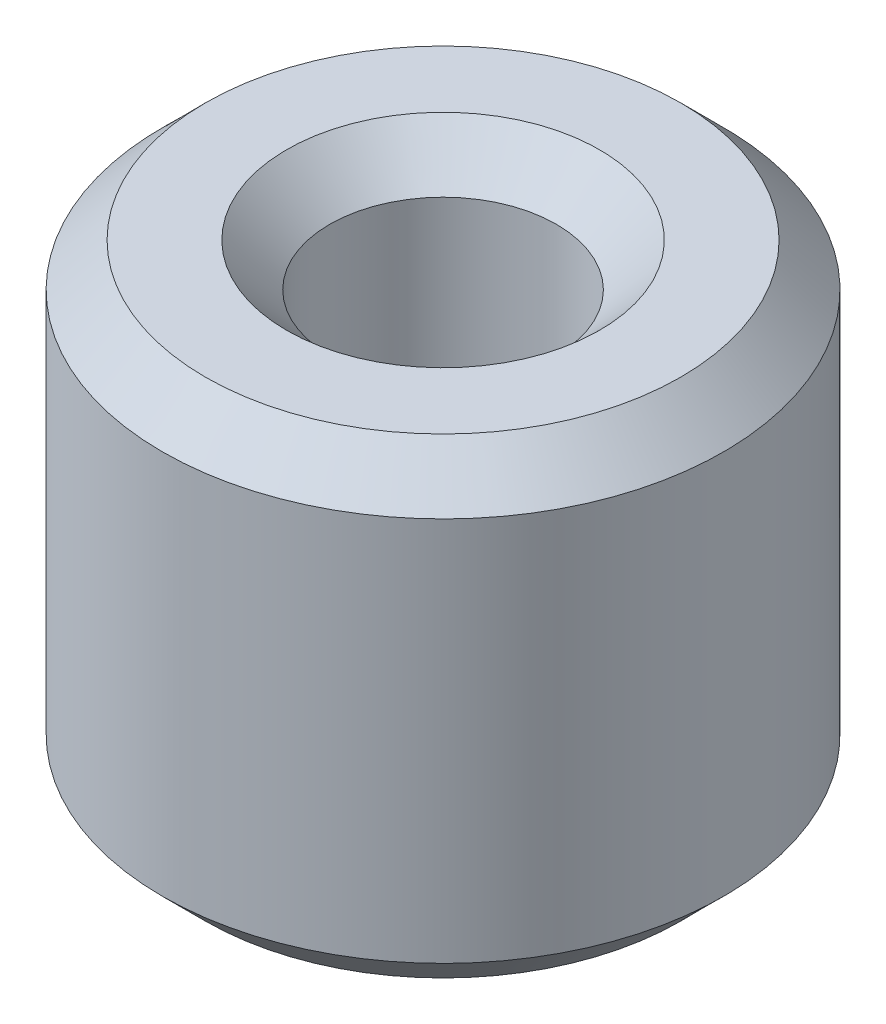
SolidWorks part; units mm, degrees
ref_plane "Front Plane" through (0, 0, 0) normal (0, 0, 1) x (1, 0, 0)
ref_plane "Top Plane" through (0, 0, 0) normal (0, 1, 0) x (1, 0, 0)
ref_plane "Right Plane" through (0, 0, 0) normal (1, 0, 0) x (0, 0, -1)
sketch "Sketch1" plane through (0, 0, 0) normal (0, 1, 0) x (1, 0, 0)
  circle A0 centre (0, 0) radius 22.5
  dimension "SLEEVE_OD" = 45
extrude "Boss-Extrude1" add sketch "Sketch1" along normal blind 37.7626
sketch "Sketch2" plane through (0, 0, 0) normal (0, 1, 0) x (1, 0, 0)
  circle A0 centre (0, 0) radius 9.0892
  dimension "BORE_D" = 18.1783
extrude "Cut-Extrude1" cut sketch "Sketch2" along normal through all
chamfer "Chamfer1" distance 3.4534 angle 45 4 edges at (0, 37.7626, 9.0892) (0, 0, 9.0892) (0, 0, 22.5) (0, 37.7626, 22.5)
